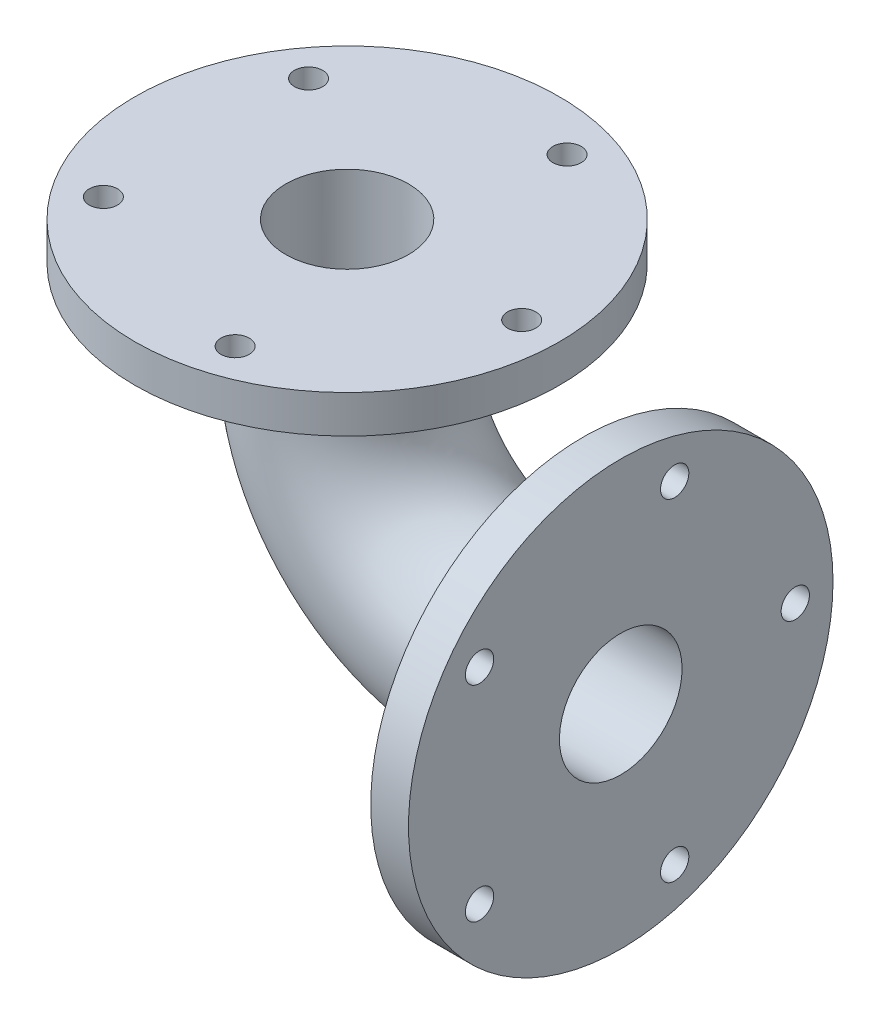
SolidWorks part; units mm, degrees
ref_plane "Front Plane" through (0, 0, 0) normal (0, 0, 1) x (1, 0, 0)
ref_plane "Top Plane" through (0, 0, 0) normal (0, 1, 0) x (1, 0, 0)
ref_plane "Right Plane" through (0, 0, 0) normal (1, 0, 0) x (0, 0, -1)
sketch "Sketch1" plane through (0, 0, 0) normal (0, 0, 1) x (1, 0, 0)
  line L0 (0, 0) -> (-55, 0)
  line L1 (-145, 90) -> (-145, 150)
  arc A0 (-55, 0) -> (-145, 90) centre (-55, 90) cw
  dimension "D1" = 90
  dimension "D2" = 145
  dimension "D3" = 150
sketch "Sketch2" plane through (0, 0, 0) normal (1, 0, 0) x (0, 0, -1)
  circle A0 centre (0, 0) radius 48.5
  dimension "D1" = 97
sweep "Sweep1" add profiles "Sketch2" path "Sketch1"
sketch "Sketch3" plane through (0, 0, 0) normal (1, 0, 0) x (0, 0, -1)
  circle A0 centre (0, 0) radius 112.5
  dimension "D1" = 225
extrude "Boss-Extrude1" add sketch "Sketch3" against normal blind 20
sketch "Sketch4" plane through (0, 150, 0) normal (0, 1, 0) x (1, 0, 0)
  circle A0 centre (-145, 0) radius 112.5
  dimension "D1" = 225
extrude "Boss-Extrude2" add sketch "Sketch4" against normal blind 20
sketch "Sketch5" plane through (0, 0, 0) normal (1, 0, 0) x (0, 0, -1)
  circle A0 centre (0, 0) radius 32.5
  dimension "D1" = 65
sweep "Cut-Sweep1" cut profiles "Sketch5" path "Sketch1<2>"
sketch "Sketch1<2>" plane through (0, 0, 0) normal (0, 0, 1) x (1, 0, 0) same geometry as "Sketch1"
sketch "Sketch6" plane through (0, 150, 0) normal (0, 1, 0) x (1, 0, 0)
  circle A0 centre (-145, 0) radius 92.5
  circle A1 centre (-52.5, 0) radius 7.5
  circle A2 centre (-116.4159, -87.9727) radius 7.5
  circle A3 centre (-219.8341, -54.3701) radius 7.5
  circle A4 centre (-219.8341, 54.3701) radius 7.5
  circle A5 centre (-116.4159, 87.9727) radius 7.5
  point P15 (-145, 0)
  dimension "D1" = 185
  dimension "D2" = 15
  dimension "D3" = 5
extrude "Cut-Extrude1" cut sketch "Sketch6" against normal blind 30 contours A4 | A5 | A1 | A2 | A3
sketch "Sketch7" plane through (0, 0, 0) normal (1, 0, 0) x (0, 0, -1)
  circle A0 centre (0, 0) radius 92.5 construction
  circle A1 centre (92.5, 0) radius 7.5
  circle A2 centre (28.5841, -87.9727) radius 7.5
  circle A3 centre (-74.8341, -54.3701) radius 7.5
  circle A4 centre (-74.8341, 54.3701) radius 7.5
  circle A5 centre (28.5841, 87.9727) radius 7.5
  point P5 (0, 0)
  point P15 (0, 0)
  dimension "D1" = 185
  dimension "D2" = 15
  dimension "D3" = 5
extrude "Cut-Extrude3" cut sketch "Sketch7" against normal blind 30
